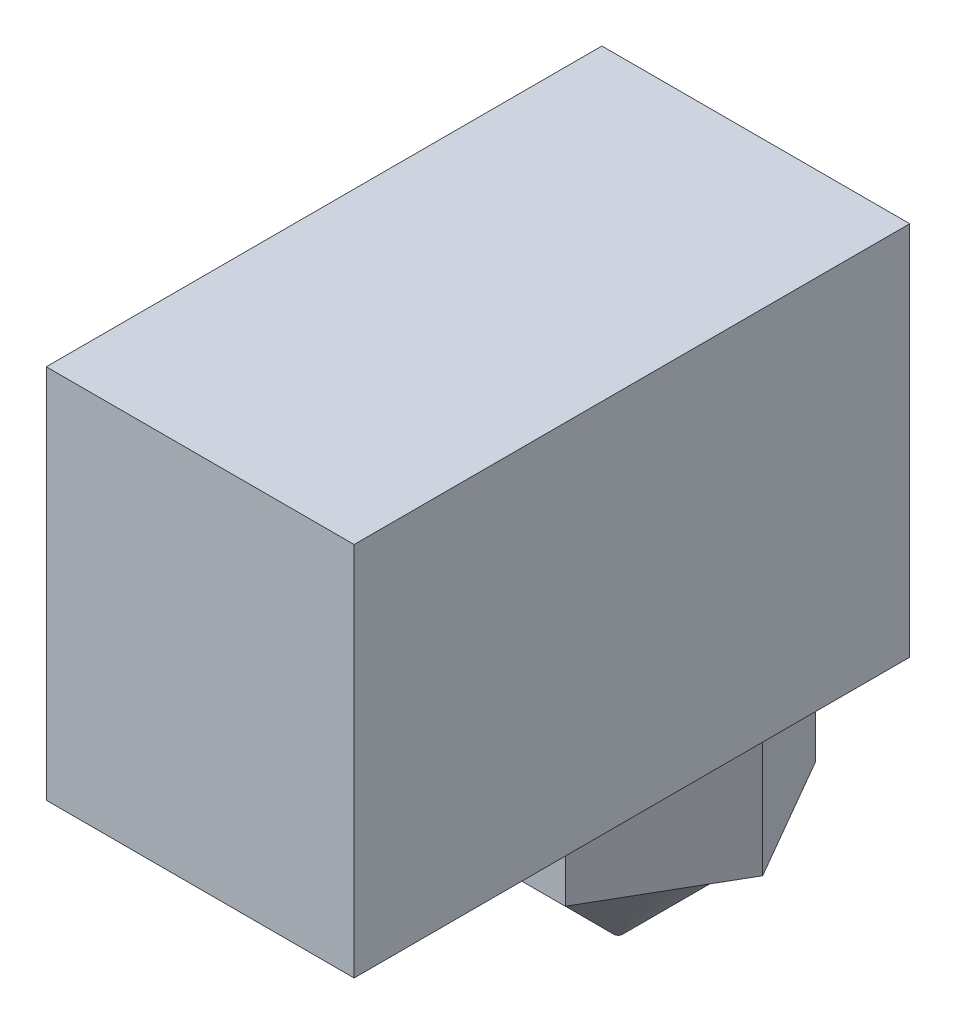
SolidWorks part; units mm, degrees
ref_plane "Front Plane" through (0, 0, 0) normal (0, 0, 1) x (1, 0, 0)
ref_plane "Top Plane" through (0, 0, 0) normal (0, 1, 0) x (1, 0, 0)
ref_plane "Right Plane" through (0, 0, 0) normal (1, 0, 0) x (0, 0, -1)
sketch "Sketch1" plane through (0, 0, 0) normal (0, 1, 0) x (1, 0, 0)
  line L1 (5.7735, 0) -> (2.8868, 5)
  line L2 (2.8868, 5) -> (-2.8868, 5)
  line L3 (-2.8868, 5) -> (-5.7735, 0)
  line L4 (-5.7735, 0) -> (-2.8868, -5)
  line L5 (-2.8868, -5) -> (2.8868, -5)
  line L6 (2.8868, -5) -> (5.7735, 0)
  circle A0 centre (0, 0) radius 5 construction
  dimension "D1" = 10
extrude "Boss-Extrude1" add sketch "Sketch1" against normal blind 5
sketch "Sketch3" plane through (0, 0, 0) normal (0, 0, 1) x (1, 0, 0)
  line L0 (0, -5) -> (0, -10)
  line L1 (-2.8868, -5) -> (2.8868, -5) construction
  line L2 (0, -10) -> (-5, -5)
  line L3 (-5.7735, -5) -> (-2.8868, -5) construction
  line L4 (-5, -5) -> (0, -5)
  dimension "D1" = 45
  dimension "D2" = 5
revolve "Revolve1" add sketch "Sketch3" angle 360 about L0
sketch "Sketch4" plane through (0, 0, 0) normal (0, 1, 0) x (1, 0, 0)
  circle A0 centre (0, 0) radius 0.175
  dimension "D1" = 0.35
extrude "Cut-Extrude1" cut sketch "Sketch4" against normal through all
sketch "Sketch5" plane through (0, 0, 0) normal (0, 1, 0) x (1, 0, 0)
  line L0 (0, -5.5) -> (0, 5.5) construction
  line L1 (-6.15, 5.5) -> (6.15, 5.5)
  line L2 (-6.15, 5.5) -> (-6.15, -16.7)
  line L3 (-6.15, -16.7) -> (6.15, -16.7)
  line L4 (6.15, 5.5) -> (6.15, -16.7)
  point P4 (0, 5.5)
  dimension "D1" = 22.2
  dimension "D2" = 12.3
  dimension "D3" = 5.5
extrude "Boss-Extrude2" add sketch "Sketch5" along normal blind 15 separate body
